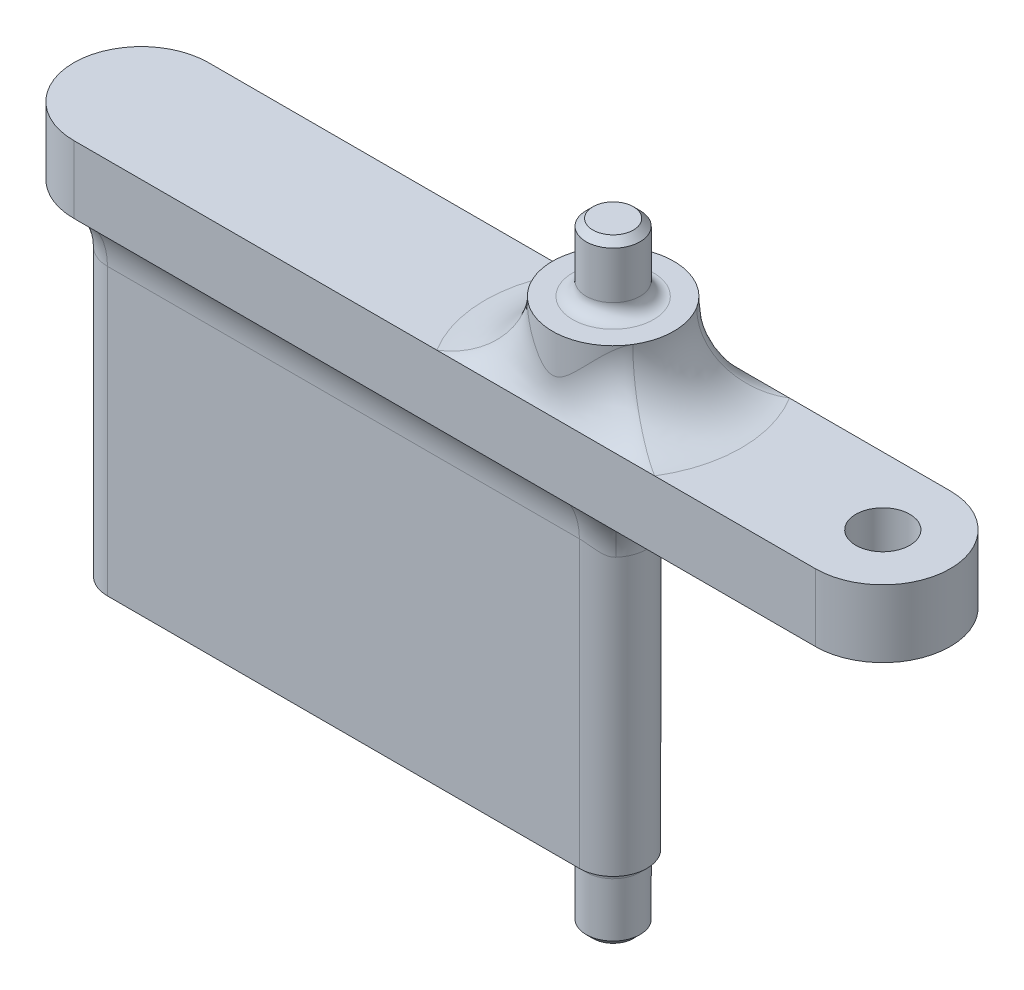
SolidWorks part; units mm, degrees
ref_plane "Front Plane" through (0, 0, 0) normal (0, 0, 1) x (1, 0, 0)
ref_plane "Top Plane" through (0, 0, 0) normal (0, 1, 0) x (1, 0, 0)
ref_plane "Right Plane" through (0, 0, 0) normal (1, 0, 0) x (0, 0, -1)
sketch "Sketch1" plane through (0, 0, 0) normal (0, 1, 0) x (1, 0, 0)
  line L0 (0, 0) -> (-70, 0) construction
  line L1 (0, -5) -> (-70, -5)
  line L2 (0, 5) -> (-70, 5)
  arc A0 (0, -5) -> (0, 5) centre (0, 0) ccw
  arc A1 (-70, 5) -> (-70, -5) centre (-70, 0) ccw
  point P3 (-35, 0)
  dimension "D1" = 70
  dimension "D2" = 10
extrude "Boss-Extrude1" add sketch "Sketch1" against normal blind 51
sketch "Sketch2" plane through (0, 0, 0) normal (0, 1, 0) x (1, 0, 0)
  line L0 (0, 0) -> (-70, 0) construction
  line L5 (0, -10) -> (-70, -10)
  line L6 (0, 10) -> (-70, 10)
  line L7 (0, 0) -> (40, 0) construction
  line L8 (0, 10) -> (40, 10)
  line L9 (0, -10) -> (40, -10)
  arc A5 (-70, 10) -> (-70, -10) centre (-70, 0) ccw
  arc A7 (40, -10) -> (40, 10) centre (40, 0) ccw
  circle A8 centre (40, 0) radius 4
  dimension "D5" = 8
  dimension "D7" = 10
  dimension "D1" = 70
  dimension "D2" = 20
  dimension "D3" = 20
  dimension "D4" = 40
  dimension "D6" = 70
extrude "Boss-Extrude2" add sketch "Sketch2" along normal blind 10
fillet "Fillet1" radius 10 1 edges at (5, 0, 0)
sketch "Sketch3" plane through (0, 10, 0) normal (0, 1, 0) x (1, 0, 0)
  circle A0 centre (0, 0) radius 9
  dimension "D1" = 18
extrude "Boss-Extrude3" add sketch "Sketch3" along normal blind 10
fillet "Fillet2" radius 10 1 edges at (0, 10, 9)
sketch "Sketch7" plane through (0, -51, 0) normal (0, -1, 0) x (1, 0, 0)
  circle A0 centre (0, 0) radius 4
  dimension "D1" = 8
extrude "Boss-Extrude4" add sketch "Sketch7" along normal blind 10
chamfer "Chamfer1" distance 1 angle 45 1 edges at (0, -61, -4)
sketch "Sketch8" plane through (0, 20, 0) normal (0, 1, 0) x (1, 0, 0)
  circle A1 centre (0, 0) radius 4
  dimension "D1" = 8
extrude "Boss-Extrude5" add sketch "Sketch8" along normal blind 10
chamfer "Chamfer2" distance 1 angle 45 1 edges at (0, 30, 4)
fillet "Fillet4" radius 1 1 edges at (0, -51, 4)
fillet "Fillet5" radius 2 1 edges at (0, 20, 4)
